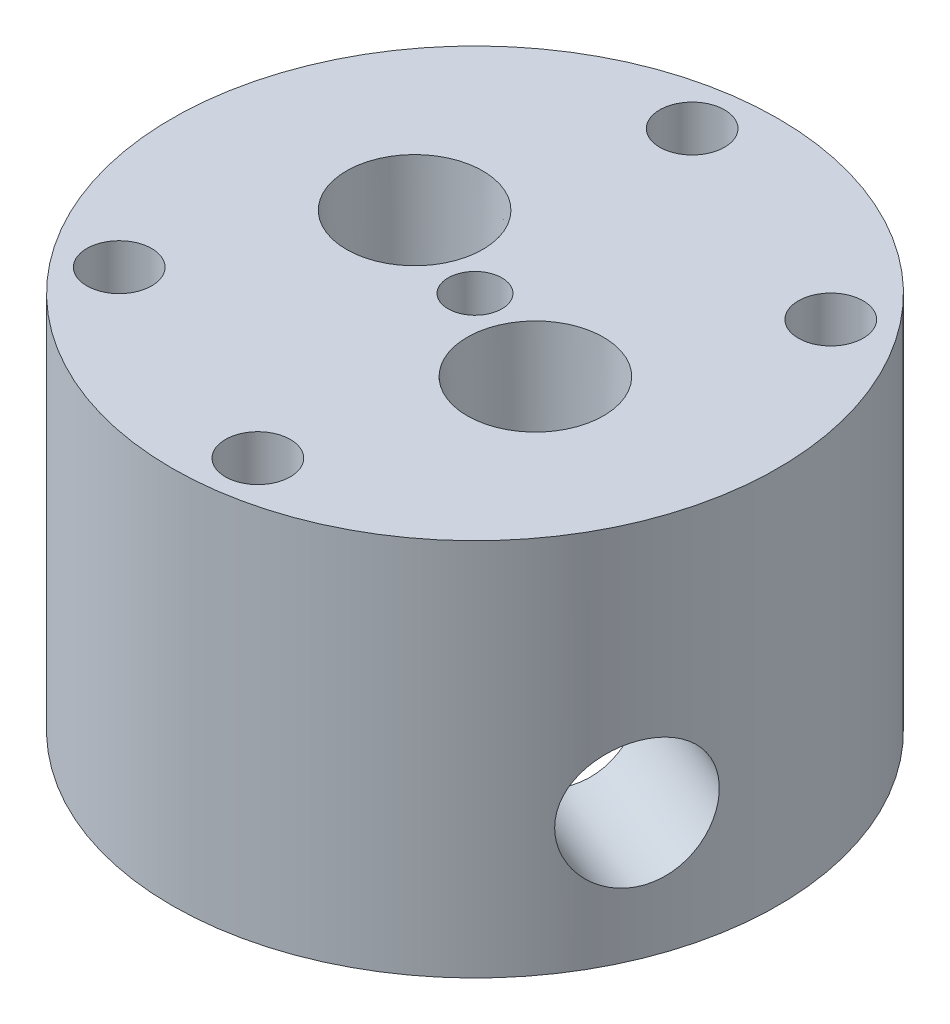
SolidWorks part; units mm, degrees
note: '?' marks a value the reader was unsure of.
material "AISI 316 Annealed Stainless Steel Bar (SS)"
ref_plane "Front Plane" through (0, 0, 0) normal (0, 0, 1) x (1, 0, 0)
ref_plane "Top Plane" through (0, 0, 0) normal (0, 1, 0) x (1, 0, 0)
ref_plane "Right Plane" through (0, 0, 0) normal (1, 0, 0) x (0, 0, -1)
sketch "Sketch1" plane through (0, 0, 0) normal (0, 1, 0) x (1, 0, 0)
  circle A0 centre (0, 0) radius 30.48
  dimension "D1" = 60.96
extrude "Boss-Extrude1" add sketch "Sketch1" along normal blind 25.4
sketch "Sketch2" plane through (0, 25.4, 0) normal (0, 1, 0) x (1, 0, 0)
  line L1 (28.9535, 9.525) -> (38.1537, 9.525)
  line L2 (28.9535, 9.525) -> (28.9535, -9.525)
  line L3 (28.9535, -9.525) -> (38.1537, -9.525)
  line L4 (38.1537, 9.525) -> (38.1537, -9.525)
  circle A0 centre (0, 0) radius 30.48 construction
  dimension "D1" = 19.05
extrude "Cut-Extrude1" [suppressed] cut sketch "Sketch2" against normal through all
hole_wizard "1/2 NPT Tapped Hole1" [suppressed] positions "Sketch5" profile "Sketch6" size "1/2" standard "ANSI Inch"
sketch "Sketch5" [suppressed] plane through (28.9535, 0, 0) normal (1, 0, 0) x (0, 0, -1)
  line L0 (9.525, 31.75) -> (-9.525, 0) construction
  point P6 (0, 15.875)
sketch "Sketch6" plane through (28.9535, 15.875, 0) normal (0, 1, 0) x (0, 0, -1)
  line L0 (0, 0) -> (0, 20.6045)
  line L1 (8.9281, 15.24) -> (0, 20.6045)
  line L2 (-8.9281, 15.24) -> (0, 20.6045) construction
  line L3 (8.9281, 15.24) -> (8.9281, 13.462)
  line L4 (8.9281, 13.462) -> (10.2617, 13.462)
  line L5 (10.2617, 13.462) -> (10.6647, 0)
  line L6 (-10.2617, 13.462) -> (-10.6647, 0) construction
  line L7 (10.6647, 0) -> (0, 0)
  line L8 (0, -6.35) -> (0, 107.95) construction
  line L11 (-8.9281, 13.462) -> (-10.2617, 13.462) construction
  dimension "Tap Drill Dia." = 17.8562
  dimension "Tap Drill Depth" = 15.24
  dimension "Thread Dia." = 21.3295
  dimension "Thread Angle" = 3.43
  dimension "Thread Depth" = 13.462
  dimension "Drill Angle" = 118
sketch "Sketch7" plane through (0, 0, 0) normal (0, -1, 0) x (1, 0, 0)
  circle A0 centre (0, 0) radius 11.43
  dimension "D1" = 22.86
extrude "Cut-Extrude2" cut sketch "Sketch7" against normal blind 12.7
hole_wizard "1/4 Clearance Hole1" positions "Sketch8" profile "Sketch9" hole size "1/4" standard "ANSI Inch" end condition through all
sketch "Sketch8" plane through (0, 25.4, 0) normal (0, 1, 0) x (1, 0, 0)
  point P3 (20.1755, 15.6153)
  point P6 (3.4355, -25.2801)
  point P11 (-3.4355, 25.2801)
  point P14 (-20.1755, -15.6153)
sketch "Sketch9" plane through (20.1755, 25.4, -15.6153) normal (1, 0, 0) x (0, 0, 1)
  line L0 (0, 0) -> (0, 25.4)
  line L1 (0, 25.4) -> (3.2639, 25.4)
  line L2 (3.2639, 25.4) -> (3.2639, 0)
  line L5 (3.2639, 0) -> (0, 0)
  line L11 (0, -6.35) -> (0, 107.95) construction
  dimension "Thru Hole Dia." = 6.5278
  dimension "Thru Hole Depth" = 25.4
hole_wizard "1/4-28 Tapped Hole1" positions "Sketch3" profile "Sketch4" tap size "1/4-28" standard "ANSI Inch" end condition through all
sketch "Sketch3" plane through (0, 25.4, 0) normal (0, 1, 0) x (1, 0, 0)
  point P0 (0, 0)
sketch "Sketch4" plane through (0, 25.4, 0) normal (1, 0, 0) x (0, 0, 1)
  line L0 (0, 0) -> (0, 25.4)
  line L1 (0, 25.4) -> (2.7051, 25.4)
  line L2 (2.7051, 25.4) -> (2.7051, 0)
  line L5 (2.7051, 0) -> (0, 0)
  line L11 (0, -6.35) -> (0, 107.95) construction
  dimension "Thru Tap Drill Dia." = 5.4102
  dimension "Thru Tap Drill Depth" = 25.4
cosmetic thread "Hole Thread1" parameters "D2"=6.35
sketch "nipple-layout" plane through (0, 25.4, 0) normal (0, 1, 0) x (1, 0, 0)
  line L0 (-18.8349, 7.7098) -> (18.8349, -7.7098) construction
  line L1 (-20.1755, -15.6153) -> (3.4355, -25.2801) construction
  circle A0 centre (0, 0) radius 7.9375 construction
  circle A1 centre (-18.8349, 7.7098) radius 11.9062 construction
  point P5 (0, 0)
  dimension "D1" = 15.875
  dimension "D2" = 23.8125
  dimension "D3" = 0.508
hole_wizard "1/4 NPT Tapped Hole1" positions "Sketch11" profile "Sketch12" size "1/4" standard "ANSI Inch" end condition through all
sketch "Sketch11" plane through (0, 25.4, 0) normal (0, 1, 0) x (1, 0, 0)
  line L0 (-10.2842, 4.2097) -> (10.2842, -4.2097) construction
  line L2 (-3.4355, 25.2801) -> (20.1755, 15.6153) construction
  line L3 (20.1755, 15.6153) -> (8.37, 20.4477) construction
  line L4 (8.37, 20.4477) -> (0, 0) construction
  circle A0 centre (10.2842, -4.2097) radius 11.1125 construction
  circle A1 centre (-10.2842, 4.2097) radius 11.1125 construction
  point P9 (-10.2842, 4.2097)
  point P10 (10.2842, -4.2097)
  point P12 (0, 0)
  dimension "D1" = 22.225
sketch "Sketch12" plane through (-10.2842, 25.4, -4.2097) normal (1, 0, 0) x (0, 0, 1)
  line L0 (0, 0) -> (0, 25.4)
  line L1 (0, 25.4) -> (5.5626, 25.4)
  line L2 (-6.558, 9.906) -> (-6.8546, 0) construction
  line L3 (5.5626, 25.4) -> (5.5626, 9.906)
  line L4 (5.5626, 9.906) -> (6.558, 9.906)
  line L5 (6.558, 9.906) -> (6.8546, 0)
  line L7 (6.8546, 0) -> (0, 0)
  line L8 (0, -6.35) -> (0, 107.95) construction
  line L11 (-5.5626, 9.906) -> (-6.558, 9.906) construction
  dimension "Thru Tap Drill Dia." = 11.1252
  dimension "Thru Tap Drill Depth" = 25.4
  dimension "Thread Dia." = 13.7092
  dimension "Thread Angle" = 3.43
  dimension "Thread Depth" = 9.906
sketch "Sketch13" plane through (0, 0, 0) normal (0, -1, 0) x (1, 0, 0)
  circle A0 centre (0, 0) radius 17.145
  dimension "D1" = 34.29
extrude "Cut-Extrude3" cut sketch "Sketch13" against normal up to surface (12.7 mm away) up to face at (0, 12.7, 0)
sketch "Sketch16" plane through (0, 25.4, 0) normal (0, 1, 0) x (1, 0, 0)
  line L0 (-22.2602, 9.112) -> (22.2602, -9.112) construction
  line L1 (-3.4355, 25.2801) -> (20.1755, 15.6153) construction
  line L2 (8.37, 20.4477) -> (0, 0) construction
  point P2 (0, 0)
other "Move Face1" face at (0, 0, -17.145) parameters "D1"=12.7
ref_axis "Axis1" through (0, 12.7, 0) along (0, 1, 0)?
ref_plane "Plane1" through (0, 0, 0) normal (-0.9255, 0, -0.3788) x (-0.3788, 0, 0.9255)
sketch "Sketch17" plane through (0, 0, 0) normal (-0.9255, 0, -0.3788) x (-0.3788, 0, 0.9255)
  line L0 (0, -12.7) -> (0, 12.7) construction
  line L1 (-17.145, -12.7) -> (17.145, -12.7) construction
  line L2 (-2.7051, 12.7) -> (2.7051, 12.7) construction
  circle A0 centre (0, 0) radius 6.35
  point P9 (0, 0)
  dimension "D1" = 12.7
extrude "Cut-Extrude4" cut sketch "Sketch17" against normal through all both and the other way through all
